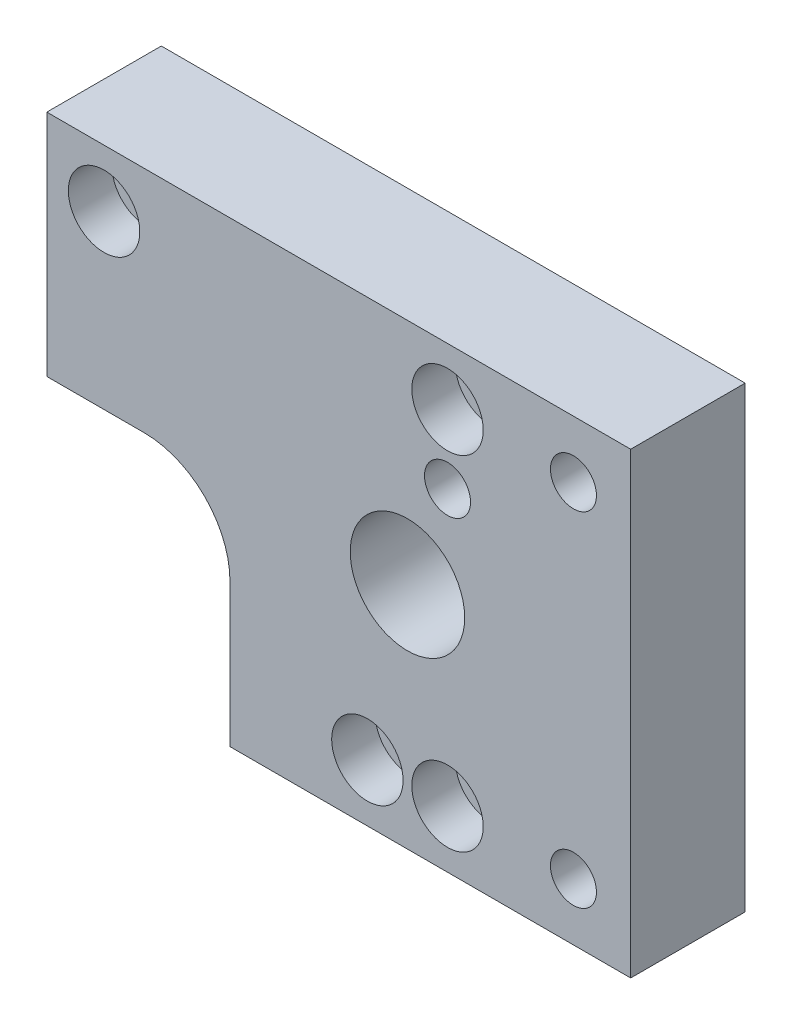
SolidWorks part; units mm, degrees
material "1060 Alloy"
ref_plane "Front Plane" through (0, 0, 0) normal (0, 0, 1) x (1, 0, 0)
ref_plane "Top Plane" through (0, 0, 0) normal (0, 1, 0) x (1, 0, 0)
ref_plane "Right Plane" through (0, 0, 0) normal (1, 0, 0) x (0, 0, -1)
sketch "Sketch1" plane through (0, 0, 0) normal (0, 0, 1) x (1, 0, 0)
  line L0 (0, 25.4) -> (0, 0) construction
  line L1 (-25.4, -25.4) -> (39.37, -25.4)
  line L2 (-25.4, -25.4) -> (-25.4, 25.4)
  line L3 (-25.4, 25.4) -> (39.37, 25.4)
  line L4 (39.37, -25.4) -> (39.37, 25.4)
  line L7 (39.37, 0) -> (-25.4, 0) construction
  circle A0 centre (-19.05, 19.05) radius 2.5527
  circle A1 centre (19.05, 19.05) radius 2.5527
  circle A2 centre (19.05, -19.05) radius 2.5527
  circle A3 centre (10.16, -19.05) radius 2.5527
  circle A4 centre (14.605, 0) radius 6.35
  point P0 (0, 0)
  dimension "D3" = 5.1054
  dimension "D7" = 12.7
  dimension "D1" = 64.77
  dimension "D2" = 50.8
  dimension "D4" = 38.1
  dimension "D5" = 6.35
  dimension "D6" = 4.445
  dimension "D8" = 38.1
  dimension "D9" = 8.89
  dimension "D10" = 25.4
extrude "Boss-Extrude1" add sketch "Sketch1" along normal blind 12.7
hole_wizard "#7 (0.201) Diameter Hole1" positions "Sketch4" profile "Sketch5" hole size "#7" standard "ANSI Inch"
sketch "Sketch4" plane through (-24.7212, -12.8643, 0) normal (0, 0, 1) x (1, 0, 0)
  line L0 (64.0912, -12.5357) -> (64.0912, 38.2643) construction
  line L2 (64.0912, 38.2643) -> (-0.6788, 38.2643) construction
  circle A5 centre (43.7712, -6.1857) radius 2.5527 construction
  circle A6 centre (43.7712, -6.1857) radius 2.5527 construction
  circle A7 centre (43.7712, 31.9143) radius 2.5527 construction
  circle A8 centre (43.7712, 31.9143) radius 2.5527 construction
  point P0 (57.7412, -6.1857)
  point P7 (57.7412, 31.9143)
  point P33 (43.7712, 24.2943)
  dimension "D3" = 7.62
  dimension "D1" = 6.35
  dimension "D2" = 6.35
sketch "Sketch5" plane through (33.02, -19.05, 0) normal (1, 0, 0) x (0, 1, 0)
  line L0 (0, 0) -> (0, 71.6378)
  line L1 (0, 71.6378) -> (2.5527, 70.104)
  line L2 (2.5527, 70.104) -> (2.5527, 0)
  line L5 (2.5527, 0) -> (0, 0)
  line L10 (0, 71.6378) -> (-2.5527, 70.104) construction
  line L11 (0, -6.35) -> (0, 107.95) construction
  dimension "Hole Dia." = 5.1054
  dimension "Hole Depth" = 70.104
  dimension "Drill Angle" = 118
sketch "Sketch6" plane through (0, 0, 12.7) normal (0, 0, -1) x (-1, 0, 0)
  circle A0 centre (-19.05, 19.05) radius 3.9624
  circle A3 centre (-19.05, -19.05) radius 3.9624
  circle A4 centre (-10.16, -19.05) radius 3.9624
  circle A5 centre (19.05, 19.05) radius 3.9624
  dimension "D1" = 7.9248
extrude "Cut-Extrude1" cut sketch "Sketch6" along normal blind 4.826
sketch "Sketch7" plane through (0, 0, 0) normal (0, 0, -1) x (-1, 0, 0)
  line L1 (25.4, -25.4) -> (5.08, -25.4)
  line L2 (25.4, -25.4) -> (25.4, 0)
  line L3 (25.4, 0) -> (5.08, 0)
  line L4 (5.08, -25.4) -> (5.08, 0)
  dimension "D1" = 20.32
extrude "Cut-Extrude2" cut sketch "Sketch7" against normal through all
fillet "Fillet2" radius 9.525 1 edges at (-5.08, 0, 6.35)
